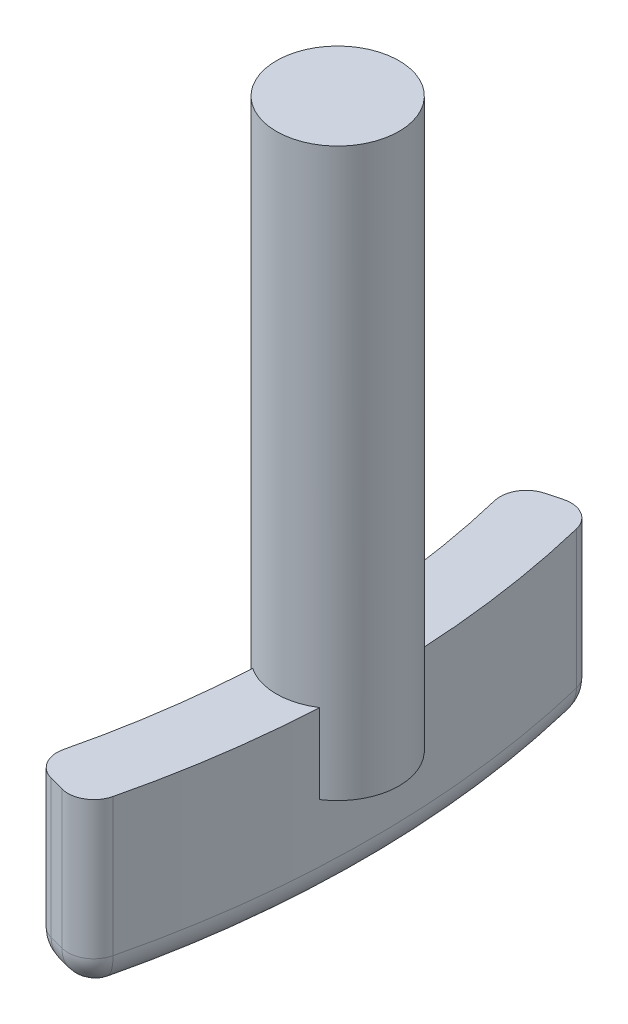
SolidWorks part; units mm, degrees
material "ABS"
ref_plane "Front Plane" through (0, 0, 0) normal (0, 0, 1) x (1, 0, 0)
ref_plane "Top Plane" through (0, 0, 0) normal (0, 1, 0) x (1, 0, 0)
ref_plane "Right Plane" through (0, 0, 0) normal (1, 0, 0) x (0, 0, -1)
sketch "Эскиз1" plane through (0, 0, 0) normal (0, 1, 0) x (1, 0, 0)
  line L16 (-0.8679, -8.0529) -> (-0.3848, -8.1824)
  line L17 (-0.8679, 8.0529) -> (-0.3848, 8.1824)
  arc A48 (-0.3848, -8.1824) -> (0.6613, -7.5615) centre (-0.1648, -7.3613) ccw
  arc A49 (0.6613, 7.5615) -> (0.6613, -7.5615) centre (-30.5354, 0) cw
  arc A50 (0.6613, 7.5615) -> (-0.3848, 8.1824) centre (-0.1648, 7.3613) ccw
  arc A51 (-0.8679, 8.0529) -> (-1.474, 7.032) centre (-0.6479, 7.2319) ccw
  arc A52 (-1.474, 7.032) -> (-1.474, -7.032) centre (-30.5354, 0) cw
  arc A53 (-0.8679, -8.0529) -> (-1.474, -7.032) centre (-0.6479, -7.2319) cw
extrude "Бобышка-Вытянуть1" add sketch "Эскиз1" along normal blind 5.6
ref_plane "Плоскость1" through (0, 3, 0) normal (0, 1, 0) x (1, 0, 0)
sketch "Эскиз2" plane through (0, 3, 0) normal (0, 1, 0) x (1, 0, 0)
  circle A2 centre (0.4313, 0) radius 2
  dimension "D1" = 4
extrude "Бобышка-Вытянуть2" add sketch "Эскиз2" along normal blind 18.5
fillet "Скругление1" radius 1.1 8 edges at (0.269, 0, 8.0923) (-0.6263, 0, 8.1176) (-1.3788, 0, 7.6658) (-0.6354, 0, 0) (-1.3788, 0, -7.6658) (-0.6263, 0, -8.1176) (0.269, 0, -8.0923) (1.5646, 0, 0)
